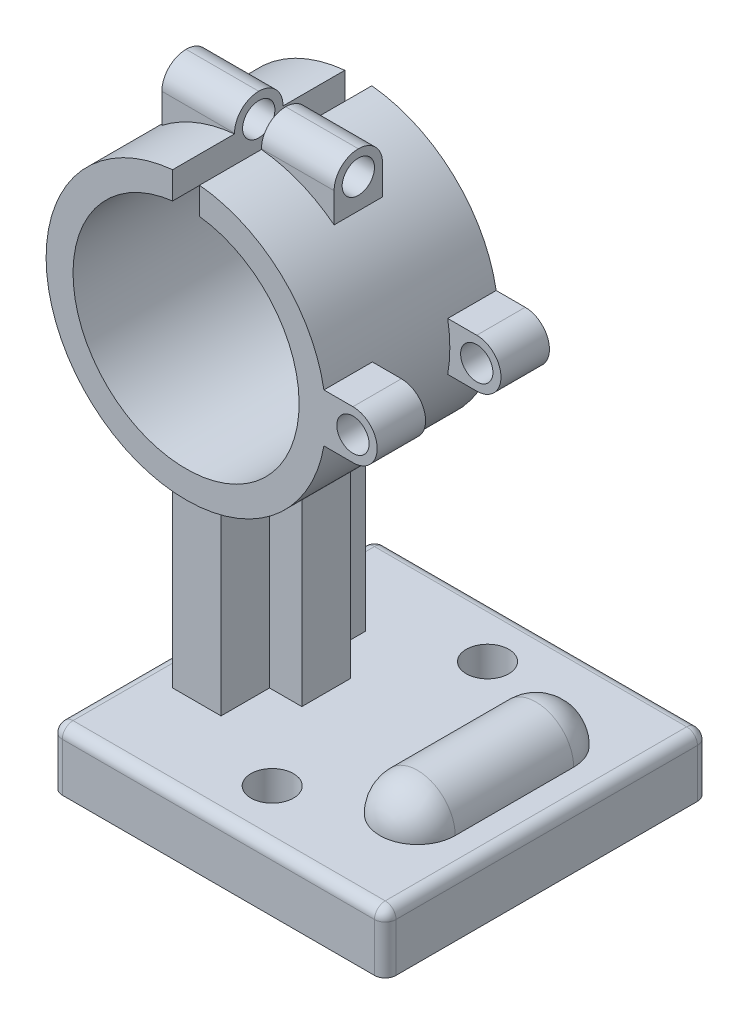
SolidWorks part; units mm, degrees
note: '?' marks a value the reader was unsure of.
ref_plane "정면" through (0, 0, 0) normal (0, 0, 1) x (1, 0, 0)
ref_plane "윗면" through (0, 0, 0) normal (0, 1, 0) x (1, 0, 0)
ref_plane "우측면" through (0, 0, 0) normal (1, 0, 0) x (0, 0, -1)
sketch "스케치1" plane through (0, 0, 0) normal (0, 1, 0) x (1, 0, 0)
  line L1 (-31, 30) -> (31, 30)
  line L2 (-31, 30) -> (-31, -30)
  line L3 (-31, -30) -> (31, -30)
  line L4 (31, 30) -> (31, -30)
  line L5 (-31, 30) -> (31, -30) construction
  line L6 (-31, -30) -> (31, 30) construction
  point P0 (0, 0)
  dimension "D1" = 62
  dimension "D2" = 60
extrude "보스-돌출1" add sketch "스케치1" along normal blind 11 contours L2 L3 L4 L1
sketch "스케치2" plane through (0, 11, 0) normal (0, 1, 0) x (1, 0, 0)
  line L0 (-25, 13.5) -> (-25, -13.5)
  line L1 (-25, -13.5) -> (-16, -13.5)
  line L2 (-16, -13.5) -> (-16, -4.5)
  line L3 (-16, -4.5) -> (-10, -4.5)
  line L4 (-10, -4.5) -> (-10, 4.5)
  line L5 (-10, 4.5) -> (-16.2104, 4.5)
  line L6 (-16.2104, 4.5) -> (-16.2104, 13.5)
  line L7 (-16.2104, 13.5) -> (-25, 13.5)
  point P3 (-10, 0)
  point P11 (-25, 0)
  dimension "D1" = 27
  dimension "D2" = 6
  dimension "D3" = 9
  dimension "D4" = 6
  dimension "D5" = 9
extrude "보스-돌출2" add sketch "스케치2" along normal blind 39
ref_plane "평면1" through (0, 0, 0) normal (0, 0, 1) x (1, 0, 0)
sketch "스케치3" plane through (0, 0, 0) normal (0, 0, 1) x (1, 0, 0)
  line L0 (-25, 50) -> (-16, 50) construction
  line L1 (-25, 50) -> (-16, 50)
  circle A0 centre (-20, 71) radius 26
  circle A1 centre (-20, 71) radius 21
  point P6 (0, 0)
  dimension "D1" = 52
  dimension "D2" = 42
  dimension "D3" = 71
  dimension "D4" = 5
extrude "보스-돌출3" add sketch "스케치3" along normal mid plane 32
ref_plane "평면2" through (0, 0, 16) normal (0, 0, 1) x (1, 0, 0)
sketch "스케치5" plane through (0, 0, 16) normal (0, 0, 1) x (1, 0, 0)
  line L0 (6, 71) -> (11, 71) construction
  line L1 (5.6076, 75.5) -> (11, 75.5)
  line L2 (5.6076, 66.5) -> (11, 66.5)
  circle A0 centre (-20, 71) radius 26 construction
  circle A1 centre (-20, 71) radius 26
  arc A3 (11, 66.5) -> (11, 75.5) centre (11, 71) ccw
  circle A4 centre (11, 71) radius 3
  point P5 (4.3842, 71)
  dimension "D2" = 4.5
  dimension "D3" = 6
  dimension "D1" = 31
extrude "보스-돌출4" add sketch "스케치5" against normal blind 9
ref_plane "평면3" through (0, 0, 0) normal (0, 0, 1) x (1, 0, 0)
mirror "대칭 복사1" about plane through (0, 0, 0) normal (0, 0, 1) of "보스-돌출4"
ref_plane "평면8" through (0, 0, -16) normal (0, 0, 1) x (1, 0, 0)
sketch "스케치9" plane through (0, 0, -16) normal (0, 0, 1) x (1, 0, 0)
  line L5 (-22.5, 106.4128) -> (-17.5, 106.4128)
  line L6 (-22.5, 106.4128) -> (-22.5, 85.7723)
  line L7 (-22.5, 85.7723) -> (-17.5, 85.7723)
  line L8 (-17.5, 106.4128) -> (-17.5, 85.7723)
  circle A0 centre (-20, 71) radius 21 construction
  circle A1 centre (-20, 71) radius 21
  point P7 (-20, 85.7723)
  dimension "D1" = 5
ref_plane "평면9" through (-36, 0, 0) normal (1, 0, 0) x (0, 0, -1)
extrude "컷-돌출2" cut sketch "스케치9" along normal through all both and the other way through all contours L5 L8 L7 L6
sketch "스케치11" plane through (0, 11, 0) normal (0, 1, 0) x (1, 0, 0)
  circle A0 centre (0, -20) radius 3.9485
  circle A1 centre (0, 20) radius 3.9485
  point P5 (0, 0)
  dimension "D2" = 31
  dimension "D1" = 31
  dimension "D3" = 10
  dimension "D4" = 10
extrude "컷-돌출3" cut sketch "스케치11" against normal blind 32
sketch "스케치13" plane through (0, 11, 0) normal (0, 1, 0) x (1, 0, 0)
  line L0 (18, 11) -> (18, -11) construction
  line L2 (11, 11) -> (11, -11)
  line L3 (18, 18) -> (18, -18)
  arc A0 (18, 18) -> (11, 11) centre (18, 11) ccw
  arc A1 (11, -11) -> (18, -18) centre (18, -11) ccw
  point P2 (18, 0)
  dimension "D2" = 7
  dimension "D3" = 13
revolve "회전3" add sketch "스케치13" angle 360 about L0
fillet "필렛1" radius 2 8 edges at (31, 5.5, -30) (0, 11, -30) (-31, 5.5, -30) (-31, 11, 0) (-31, 5.5, 30) (31, 5.5, 30) (0, 11, 30) (31, 11, 0)
ref_plane "평면11" through (0, 0, 0) normal (0, 0, 1) x (1, 0, 0)
sketch "스케치14" plane through (0, 0, 0) normal (0, 0, 1) x (1, 0, 0)
  line L0 (-17.5, 96.8795) -> (-17.5, 101.5)
  line L1 (-17.5, 101.5) -> (-4, 101.5)
  line L2 (-4, 101.5) -> (-4, 91.4939)
  arc A0 (5.6076, 75.5) -> (-17.5, 96.8795) centre (-20, 71) ccw construction
  arc A1 (-4, 91.4939) -> (-17.5, 96.8795) centre (-20, 71) ccw
  arc A2 (11, 66.5) -> (11, 75.5) centre (11, 71) ccw construction
  dimension "D1" = 30.5
  dimension "D2" = 16
extrude "보스-돌출6" add sketch "스케치14" along normal mid plane 9 contours L1 L2 A1 L0
fillet "필렛3" radius 4.5 2 edges at (-10.75, 101.5, -4.5) (-10.75, 101.5, 4.5)
ref_axis "기준축1" through (-20, 71, 16) along (0, 0, -1)?
ref_plane "평면12" through (-20, 0, 0) normal (1, 0, 0) x (0, 0, -1)
mirror "대칭 복사2" about plane through (-20, 0, 0) normal (1, 0, 0) of "필렛3", "보스-돌출6"
sketch "스케치15" plane through (-4, 0, 0) normal (1, 0, 0) x (0, 0, -1)
  circle A0 centre (0, 97) radius 3
  dimension "D1" = 6
extrude "컷-돌출4" cut sketch "스케치15" against normal through all
